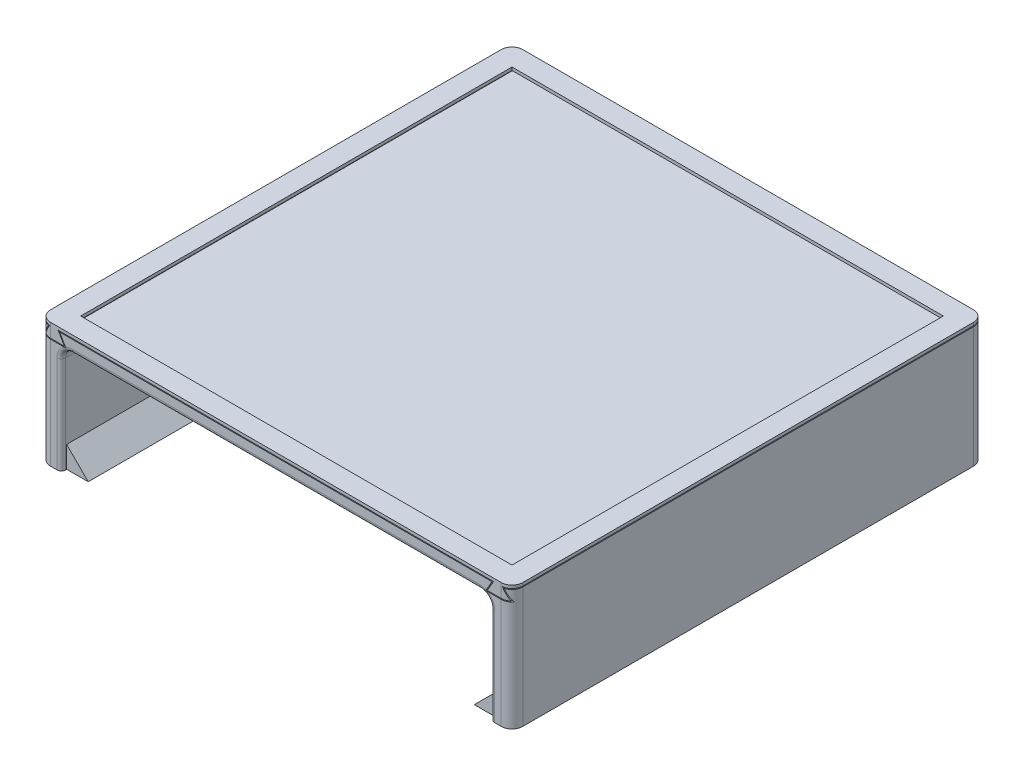
SolidWorks part; units mm, degrees
ref_plane "Front Plane" through (0, 0, 0) normal (0, 0, 1) x (1, 0, 0)
ref_plane "Top Plane" through (0, 0, 0) normal (0, 1, 0) x (1, 0, 0)
ref_plane "Right Plane" through (0, 0, 0) normal (1, 0, 0) x (0, 0, -1)
sketch "Sketch1" plane through (0, 0, 0) normal (0, 0, 1) x (1, 0, 0)
  line L0 (-99.5, -6) -> (99.5, -6)
  line L1 (-109.5, -56) -> (-99.5, -56)
  line L2 (-109.5, -56) -> (-109.5, 0)
  line L4 (-99.5, -56) -> (-99.5, -6)
  line L5 (0, -6) -> (0, 0) construction
  line L7 (-104.9204, 0.4) -> (-107.8072, -4.6)
  line L8 (-107.8072, -4.6) -> (-98.0337, -4.6)
  line L9 (-98.0337, -4.6) -> (-100.9204, 0.4)
  line L10 (-109.5, 0.4) -> (-104.9204, 0.4)
  line L14 (-100.9204, 0.4) -> (100.9204, 0.4)
  line L15 (0, 0.4) -> (0, 1.8) construction
  line L16 (109.5, 1.8) -> (-109.5, 1.8)
  line L17 (-109.5, 1.8) -> (-109.5, 0.4)
  line L18 (-105.6132, 0) -> (-108.5, -5)
  line L19 (-108.5, -5) -> (-97.3409, -5)
  line L20 (-97.3409, -5) -> (-100.2276, 0)
  line L21 (-109.5, 0) -> (-105.6132, 0)
  line L22 (-100.2276, 0) -> (100.2276, 0)
  line L23 (109.5, 1.4) -> (-109.5, 1.4) construction
  line L24 (109.5, 0) -> (105.6132, 0)
  line L25 (97.3409, -5) -> (100.2276, 0)
  line L26 (108.5, -5) -> (97.3409, -5)
  line L27 (105.6132, 0) -> (108.5, -5)
  line L28 (109.5, 1.8) -> (109.5, 0.4)
  line L29 (109.5, 0.4) -> (104.9204, 0.4)
  line L30 (98.0337, -4.6) -> (100.9204, 0.4)
  line L31 (107.8072, -4.6) -> (98.0337, -4.6)
  line L32 (104.9204, 0.4) -> (107.8072, -4.6)
  line L33 (99.5, -56) -> (99.5, -6)
  line L34 (109.5, -56) -> (109.5, 0)
  line L35 (109.5, -56) -> (99.5, -56)
  line L36 (-100.5, 0.4) -> (-100.5, 1.4) construction
  point P21 (0, 1.4)
  dimension "D1" = 109.5
  dimension "D2" = 4
  dimension "D5" = 0.4
  dimension "DovetailSpacing" = 0.4
  dimension "D6" = 0.4
  dimension "D7" = 0.4
  dimension "D8" = 5
  dimension "D3" = 60
  dimension "D4" = 60
  dimension "D9" = 0.4
  dimension "MetalSheetGap" = 1
  dimension "D10" = 1
  dimension "D11" = 10
  dimension "D12" = 1
  dimension "MainBoardSize" = 50
  dimension "D13" = 9
extrude "Boss-Extrude1" add sketch "Sketch1" along normal mid plane 219 contours L4 L0 L33 L35 L34 L24 L27 L26 L25 L22 L20 L19 L18 L21 L2 L1
extrude "Boss-Extrude2" add sketch "Sketch1<4>" along normal mid plane 219 separate body contours L16 L17 L10 L7 L8 L9 L14 L30 L31 L32 L29 L28
sketch "Sketch1<4>" plane through (0, 0, 0) normal (0, 0, 1) x (1, 0, 0) same geometry as "Sketch1"
sketch "Sketch2" plane through (0, 0.4, 0) normal (0, -1, 0) x (1, 0, 0)
  line L1 (-100, -100) -> (100, -100)
  line L2 (-100, -100) -> (-100, 100)
  line L3 (-100, 100) -> (100, 100)
  line L4 (100, -100) -> (100, 100)
  line L5 (-100, -100) -> (100, 100) construction
  line L6 (-100, 100) -> (100, -100) construction
  point P0 (0, 0)
  dimension "D1" = 200
  dimension "D2" = 200
extrude "Cut-Extrude1" cut sketch "Sketch2" against normal through all contours L3 L4 L1 L2
fillet "Fillet1" radius 5 2 edges at (99.5, -6, 0) (-99.5, -6, 0)
sketch "Sketch3" plane through (0, 0, 0) normal (0, 0, 1) x (1, 0, 0)
  line L1 (-99.5, -6) -> (99.5, -6)
  line L2 (-99.5, -6) -> (-99.5, -56)
  line L3 (-99.5, -56) -> (99.5, -56)
  line L4 (99.5, -6) -> (99.5, -56)
extrude "Boss-Extrude3" add sketch "Sketch3" along normal mid plane 10
fillet "Fillet2" radius 5 4 edges at (-109.5, -28, 109.5) (-109.5, -28, -109.5) (109.5, -28, -109.5) (109.5, -28, 109.5)
fillet "Fillet3" radius 5 4 edges at (-109.5, 1.1, -109.5) (109.5, 1.1, -109.5) (109.5, 1.1, 109.5) (-109.5, 1.1, 109.5)
fillet "Fillet4" radius 2 10 edges at (-99.5, -33.5, 109.5) (-98.0355, -7.4645, 109.5) (99.5, -33.5, 109.5) (98.0355, -7.4645, 109.5) (-99.5, -33.5, -109.5) (-98.0355, -7.4645, -109.5) (99.5, -33.5, -109.5) (98.0355, -7.4645, -109.5) (0, -6, 109.5) (0, -6, -109.5)
fillet "Fillet5" radius 1 10 edges at (-99.5, -33.5, -5) (-98.0355, -7.4645, -5) (0, -6, -5) (98.0355, -7.4645, -5) (-99.5, -33.5, 5) (-98.0355, -7.4645, 5) (0, -6, 5) (98.0355, -7.4645, 5) (99.5, -33.5, -5) (99.5, -33.5, 5)
sketch "Sketch6" plane through (0, 0, 0) normal (0, 0, 1) x (1, 0, 0)
  line L0 (-99.5, -56) -> (-89.5, -56)
  line L1 (-98.5, -56) -> (98.5, -56) construction
  line L2 (-89.5, -56) -> (-99.5, -46)
  line L3 (-99.5, -46) -> (-99.5, -56)
  dimension "D1" = 45
  dimension "D2" = 10
extrude "Boss-Extrude6" add sketch "Sketch6" against normal mid plane 214
mirror "Mirror1" about plane through (0, 0, 0) normal (1, 0, 0) of "Boss-Extrude6"
equation "\"D6@Sketch1\"=\"DovetailSpacing@Sketch1\""
equation "\"D7@Sketch1\"=\"DovetailSpacing@Sketch1\""
equation "\"D4@Sketch1\"=\"D3@Sketch1\""
equation "\"CheckerPatternThickness\"= 0.2mm * 2'How thick the squares the pecies sit on should be"
equation "\"D9@Sketch1\"=\"CheckerPatternThickness\""
equation "\"D2@Sketch2\"=\"D1@Sketch2\""
